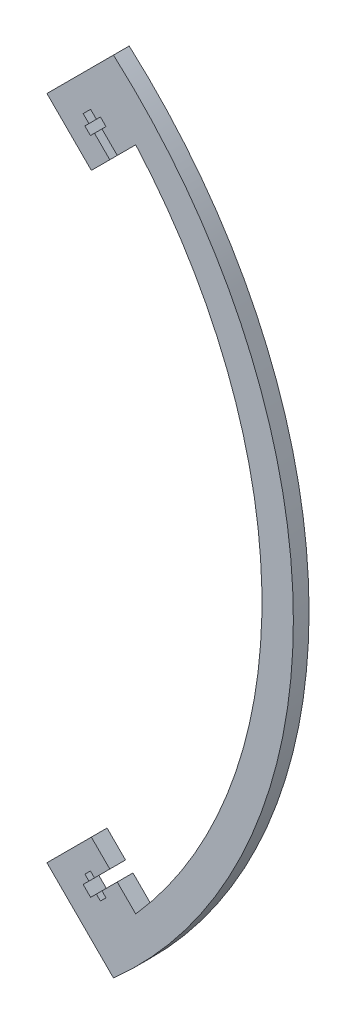
SolidWorks part; units mm, degrees
ref_plane "Front Plane" through (0, 0, 0) normal (0, 0, 1) x (1, 0, 0)
ref_plane "Top Plane" through (0, 0, 0) normal (0, 1, 0) x (1, 0, 0)
ref_plane "Right Plane" through (0, 0, 0) normal (1, 0, 0) x (0, 0, -1)
sketch "Sketch1" plane through (0, 0, 0) normal (0, 0, 1) x (1, 0, 0)
  line L0 (143.3604, 116.9193) -> (134.3442, 107.9031)
  line L1 (143.3604, -160.8213) -> (134.3442, -151.805)
  line L2 (143.3604, -160.8213) -> (128.1057, -145.5666) construction
  line L3 (128.1057, 101.6647) -> (143.3604, 116.9193) construction
  arc A0 (143.3604, 116.9193) -> (143.3604, -160.8213) centre (-21.951, -21.951) cw
  arc A1 (134.3442, 107.9031) -> (134.3442, -151.805) centre (-21.951, -21.951) cw
  arc A2 (143.3604, 116.9193) -> (-91.801, 182.3375) centre (-21.951, -21.951) ccw construction
  dimension "D1" = 12.7
extrude "Boss-Extrude1" add sketch "Sketch1" along normal blind 6.35
ref_plane "Clothes Line Center Plane" through (0, -21.951, 0) normal (0, 1, 0) x (1, 0, 0)
sketch "Sketch4" plane through (0, 0, 6.35) normal (0, 0, 1) x (1, 0, 0)
  line L0 (134.3442, -151.805) -> (143.3604, -160.8213)
  line L1 (139.4438, -165.8849) -> (130.4636, -156.9046) construction
  line L2 (105.6551, -132.0962) -> (123.6156, -150.0567) construction
  line L3 (139.194, -165.6351) -> (112.2532, -138.6943)
  line L4 (112.2532, -138.6943) -> (94.2927, -156.6548)
  line L5 (94.2927, -156.6548) -> (121.204, -183.5661)
  arc A0 (143.3604, -160.8213) -> (139.194, -165.6351) centre (-21.951, -21.951) cw
  arc A1 (134.3442, -151.805) -> (130.1981, -156.6392) centre (-21.951, -21.951) cw
  arc A2 (139.194, -165.6351) -> (121.204, -183.5661) centre (-21.951, -21.951) cw
  arc A3 (134.3442, -151.805) -> (134.3442, 107.9031) centre (-21.951, -21.951) ccw construction
  arc A4 (143.3604, -160.8213) -> (143.3604, 116.9193) centre (-21.951, -21.951) ccw construction
  arc A5 (-192.6342, 110.2612) -> (143.3604, -160.8213) centre (-21.951, -21.951) ccw construction
  line M8 (134.3442, -151.805) -> (143.3604, -160.8213)
  dimension "D1" = 25.4
  dimension "D2" = 38.1
extrude "Boss-Extrude3" add sketch "Sketch4" against normal up to surface (6.35 mm away) contours A1 L3 A0 M8 | A2 L3 L4 L5 region at (136.7864, -158.7357, 6.35) region at (116.8258, -161.2242, 6.35) up to face at (163.2257, -21.951, 0)
sketch "Sketch5" plane through (0, 0, 6.35) normal (0, 0, 1) x (1, 0, 0)
  line L0 (121.2256, -147.6667) -> (103.2651, -165.6272) construction
  line L1 (130.1981, -156.6392) -> (112.2532, -138.6943) construction
  line L2 (94.2927, -156.6548) -> (121.204, -183.5661) construction
  line L3 (130.1981, -156.6392) -> (112.2376, -174.5997)
  line L4 (112.2532, -138.6943) -> (94.2927, -156.6548) construction
  line B0 (122.7343, -149.1754) -> (119.717, -146.158)
  line B1 (111.2755, -154.5995) -> (109.6411, -152.9651)
  line B2 (109.6411, -152.9651) -> (111.8862, -150.72)
  line B3 (111.8862, -150.72) -> (113.5206, -152.3544)
  line B4 (113.5206, -152.3544) -> (119.717, -146.158)
  line B5 (111.2755, -154.5995) -> (108.9406, -156.9344)
  line B6 (108.9406, -156.9344) -> (111.958, -159.9517)
  line B7 (114.2929, -157.6169) -> (111.958, -159.9517)
  line B8 (116.5379, -155.3718) -> (122.7343, -149.1754)
  line B9 (118.1723, -157.0062) -> (116.5379, -155.3718)
  line B10 (115.9273, -159.2513) -> (118.1723, -157.0062)
  line B11 (114.2929, -157.6169) -> (115.9273, -159.2513)
  line M9 (130.1981, -156.6392) -> (112.2532, -138.6943)
sketch_block_instance "TSlot-1"
sketch_block "TSlot" parameters "D1"=3.302, "D2"=3.175
extrude "Cut-Extrude1" cut sketch "Sketch5" against normal through all contours L0 B6 B7 B11 B10 B9 B8 M9 | L0 B0 B4 B3 B2 B1 B5 B6 region at (116.5257, -154.4541, 6.35) region at (114.4382, -152.3667, 6.35)
mirror "Mirror2" about plane through (0, -21.951, 0) normal (0, 1, 0) of "Boss-Extrude3", "Cut-Extrude1"
